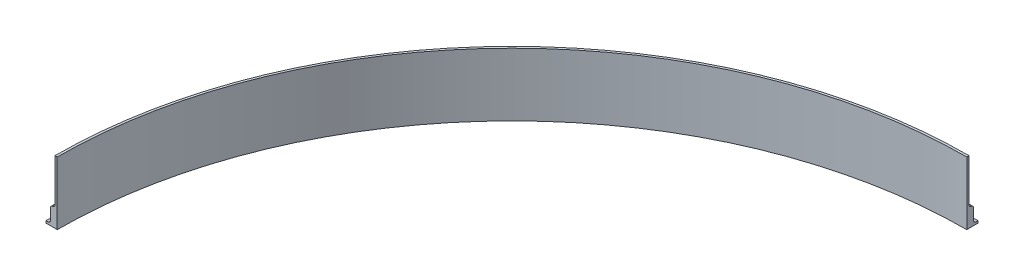
SolidWorks part; units mm, degrees
material "AISI 4340 Steel, annealed"
ref_plane "Front Plane" through (0, 0, 0) normal (0, 0, 1) x (1, 0, 0)
ref_plane "Top Plane" through (0, 0, 0) normal (0, 1, 0) x (1, 0, 0)
ref_plane "Right Plane" through (0, 0, 0) normal (1, 0, 0) x (0, 0, -1)
sketch "Sketch1" plane through (0, 0, 0) normal (0, 1, 0) x (1, 0, 0)
  line L0 (0, 0) -> (25, 0)
  line L1 (1036, 1036) -> (1036, 1011)
  arc A0 (0, 0) -> (1036, 1036) centre (1036, 0) cw
  arc A1 (25, 0) -> (1036, 1011) centre (1036, 0) cw
  dimension "D1" = 1036
  dimension "D2" = 25
extrude "Bottom level" add sketch "Sketch1" along normal blind 5
sketch "Sketch2" plane through (0, 5, 0) normal (0, 1, 0) x (1, 0, 0)
  line L0 (1036, 1011) -> (1036, 1026)
  line L1 (10, 0) -> (25, 0)
  arc A0 (1036, 1011) -> (25, 0) centre (1036, 0) ccw construction
  arc A1 (1036, 1011) -> (25, 0) centre (1036, 0) ccw
  arc A2 (1036, 1026) -> (10, 0) centre (1036, 0) ccw
  dimension "D1" = 15
extrude "Mid level" add sketch "Sketch2" along normal blind 35
sketch "Sketch3" plane through (0, 40, 0) normal (0, 1, 0) x (1, 0, 0)
  line L0 (1036, 1016) -> (1036, 1011)
  line L1 (20, 0) -> (25, 0)
  arc A0 (1036, 1011) -> (25, 0) centre (1036, 0) ccw construction
  arc A1 (1036, 1011) -> (25, 0) centre (1036, 0) ccw
  arc A2 (1036, 1016) -> (20, 0) centre (1036, 0) ccw
  dimension "D1" = 5
extrude "Guard rail" add sketch "Sketch3" along normal blind 100
fillet "Rounding" radius 5 3 edges at (317.5795, 40, -718.4205) (310.5084, 40, -725.4916) (310.5084, 5, -725.4916)
